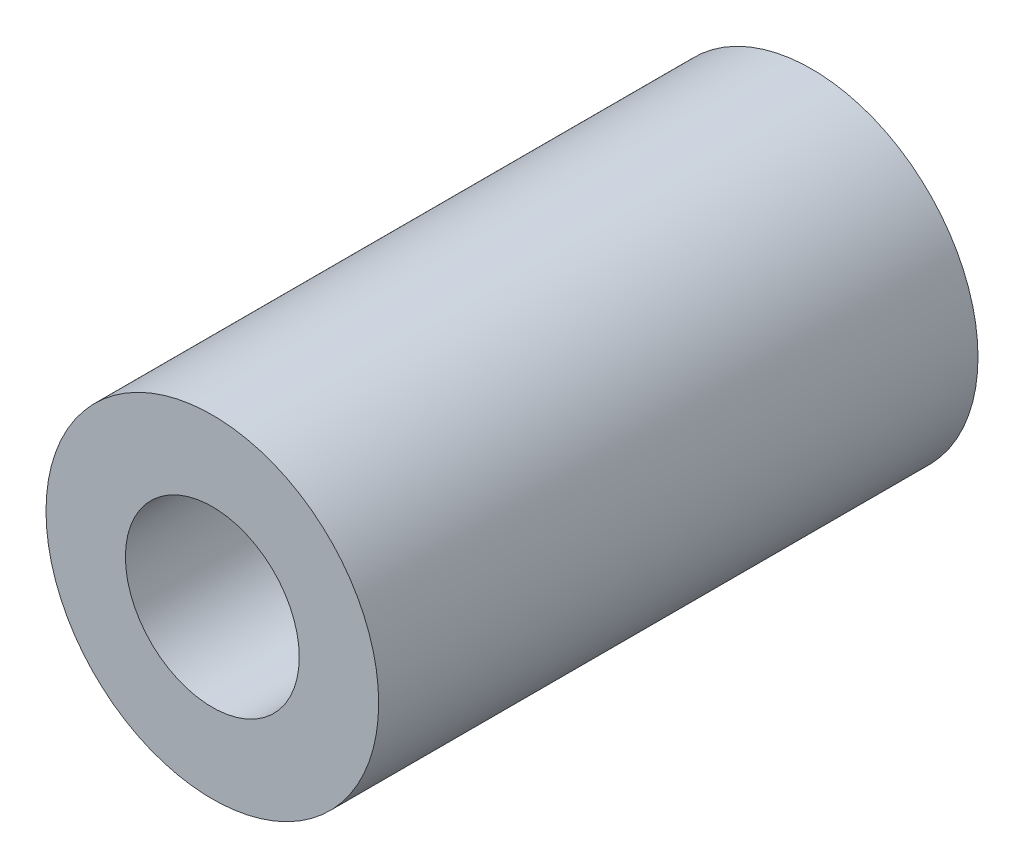
SolidWorks part; units mm, degrees
ref_plane "Front Plane" through (0, 0, 0) normal (0, 0, 1) x (1, 0, 0)
ref_plane "Top Plane" through (0, 0, 0) normal (0, 1, 0) x (1, 0, 0)
ref_plane "Right Plane" through (0, 0, 0) normal (1, 0, 0) x (0, 0, -1)
sketch "Sketch1" plane through (0, 0, 0) normal (0, 0, 1) x (1, 0, 0)
  circle A0 centre (0, 0) radius 2.4892
  circle A1 centre (0, 0) radius 4.7625
  dimension "D1" = 4.9784
  dimension "D2" = 9.525
extrude "Boss-Extrude1" add sketch "Sketch1" along normal mid plane 17.1602
